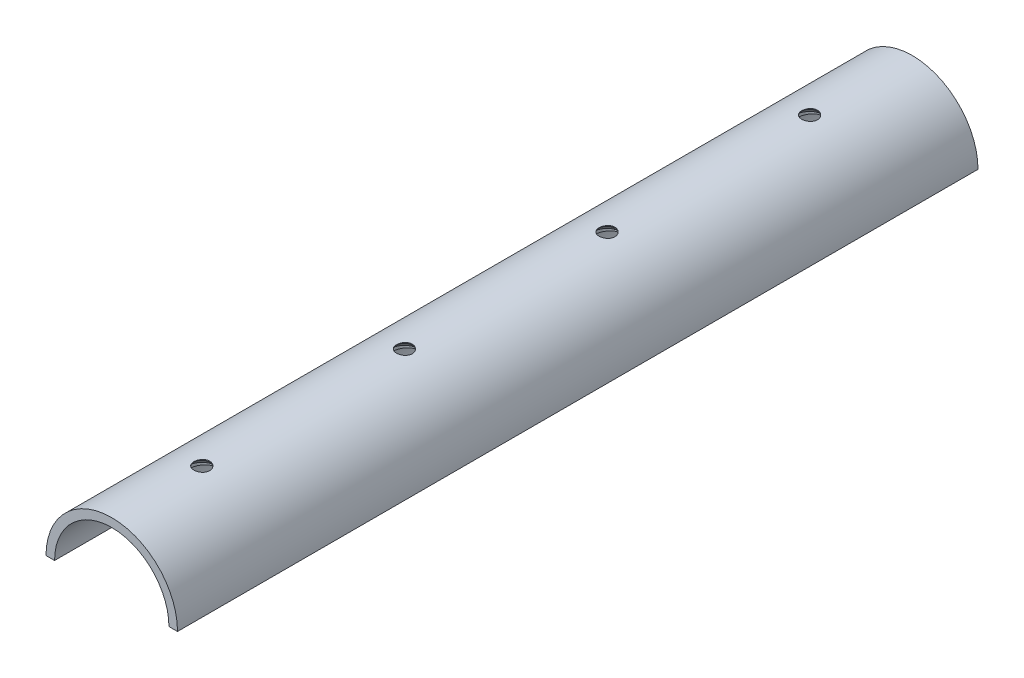
SolidWorks part; units mm, degrees
ref_plane "Front Plane" through (0, 0, 0) normal (0, 0, 1) x (1, 0, 0)
ref_plane "Top Plane" through (0, 0, 0) normal (0, 1, 0) x (1, 0, 0)
ref_plane "Right Plane" through (0, 0, 0) normal (1, 0, 0) x (0, 0, -1)
sketch "Sketch2" plane through (0, 0, 0) normal (0, 0, 1) x (1, 0, 0)
  circle A0 centre (0, 0) radius 29.21
  dimension "D1" = 58.42
extrude "Boss-Extrude1" add sketch "Sketch2" against normal blind 355.6
sketch "Sketch3" plane through (0, 0, 0) normal (0, 0, 1) x (1, 0, 0)
  circle A0 centre (0, 0) radius 25.4
  dimension "D1" = 50.8
extrude "Cut-Extrude1" cut sketch "Sketch3" against normal through all
sketch "Sketch4" plane through (0, 0, 0) normal (0, 1, 0) x (1, 0, 0)
  line L1 (-29.21, 355.6) -> (29.21, 355.6)
  line L2 (-29.21, 355.6) -> (-29.21, 0)
  line L3 (-29.21, 0) -> (29.21, 0)
  line L4 (29.21, 355.6) -> (29.21, 0)
extrude "Cut-Extrude2" cut sketch "Sketch4" against normal up to next
sketch "Sketch5" plane through (0, 0, 0) normal (0, 1, 0) x (1, 0, 0)
  line L0 (0, 40) -> (0, 130) construction
  point P0 (0, 40)
  point P4 (0, 130)
  point P7 (0, 220)
  point P8 (0, 310)
  dimension "D1" = 40
  dimension "D2" = 90
hole_wizard "CSK for M6 Flat Head Machine Screw1" positions "Sketch9" profile "Sketch10" countersink size "M6" standard "ANSI Metric" end condition through all
sketch "Sketch9" plane through (0, 0, 0) normal (0, -1, 0) x (-1, 0, 0)
  point P45 (0, 40)
  point P48 (0, 130)
  point P51 (0, 220)
  point P54 (0, 310)
sketch "Sketch10" plane through (0, 0, -40) normal (1, 0, 0) x (0, 0, -1)
  line L0 (0, 0) -> (0, 29.21)
  line L1 (0, 29.21) -> (3.5, 29.21)
  line L2 (3.5, 29.21) -> (3.5, 28.8)
  line L3 (3.5, 28.8) -> (6.3, 26)
  line L4 (6.3, 26) -> (6.3, 0)
  line L6 (6.3, 0) -> (0, 0)
  line L7 (-3.5, 28.8) -> (-6.3, 26) construction
  line L11 (0, -6.35) -> (0, 107.95) construction
  dimension "Thru Hole Dia." = 7
  dimension "Thru Hole Depth" = 29.21
  dimension "C'Sink Dia." = 12.6
  dimension "C'Sink Angle" = 90
  dimension "Head Clearance" = 26
